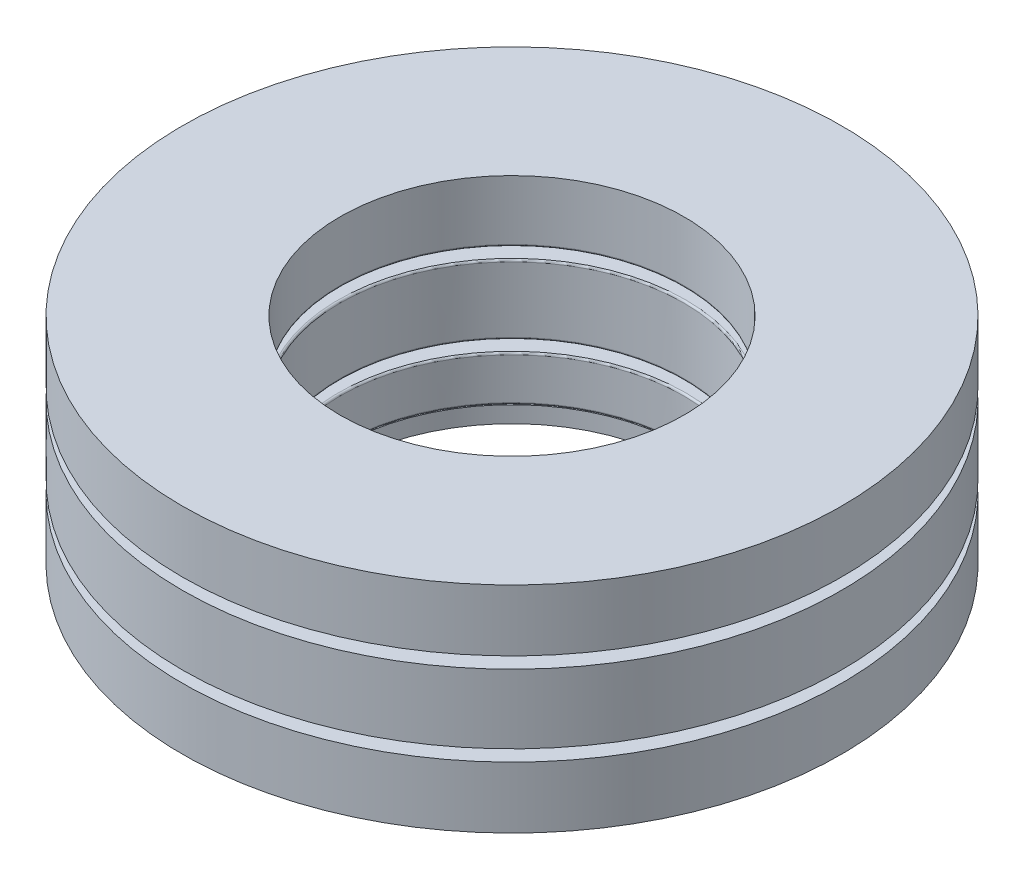
SolidWorks part; units mm, degrees
other "Imported8"
other "Imported2"
other "Imported1"
other "Imported3"
other "Imported4"
other "Imported5"
other "Imported6"
other "Imported9"
other "Imported7" parameters "Angle"=45, "Balls"=8, "D1"=8, "D2"=45, "OD"=28, "Shaft Dia"=8.0137, "Th"=8.74, "D3"=4.9022, "ID"=16.076, "E | Thickness"=4.92, "Thickness"=6.35, "Washer Thickness"=1.57, "F | Ball Diameter"=2, "Ball Diameter"=2
ref_plane "Front Plane" through (0, 0, 0) normal (0, 0, 1) x (1, 0, 0)
ref_plane "Top Plane" through (0, 0, 0) normal (0, 1, 0) x (1, 0, 0)
ref_plane "Right Plane" through (0, 0, 0) normal (1, 0, 0) x (0, 0, -1)
sketch "Sketch1" plane through (0, 0, 0) normal (0, 1, 0) x (1, 0, 0)
  circle A0 centre (0, 0) radius 12 construction
  circle A1 centre (0, 0) radius 6 construction
  circle A2 centre (0, 0) radius 9.15 construction
  dimension "OD" = 24
  dimension "Ball Circle" = 18.3
  dimension "ID" = 12
sketch "Sketch2" plane through (0, 0, 0) normal (0, 0, -1) x (-1, 0, 0)
  line L0 (-12, 3.175) -> (-12, 1.605) construction
  line L1 (-12, 0) -> (0, 0) construction
  line L3 (0, 3.175) -> (0, -3.175) construction
  line L4 (-12, 1.605) -> (-12, -1.605) construction
  line L6 (-12, -1.605) -> (-12, -3.175) construction
  point P11 (-12, 0)
sketch "Sketch3" plane through (0, 0, 0) normal (0, 0, 1) x (1, 0, 0)
  line L2 (12, 1.2038) -> (6, 1.2037)
  line L4 (12, 1.2038) -> (12, -1.2037)
  line L7 (12, -1.2037) -> (6, -1.2037)
  line L8 (6, 1.2037) -> (6, -1.2037)
  line L11 (12, 1.605) -> (12, -1.605) construction
  point P8 (6, 0)
  dimension "D1" = 2.4075
revolve "Revolve1" add sketch "Sketch3" angle 360 about L3
sketch "Sketch4" plane through (0, 0, 0) normal (0, 0, 1) x (1, 0, 0)
  line L0 (9.15, 1.605) -> (9.15, -1.605)
  arc A0 (9.15, 1.605) -> (9.15, -1.605) centre (9.15, 0) ccw
revolve "Cut-Revolve1" cut sketch "Sketch4" angle 360 about L0
sketch "Sketch5" plane through (0, 0, 0) normal (0, 0, 1) x (1, 0, 0)
  line L0 (9.15, 1.605) -> (9.15, -1.605)
  arc A0 (9.15, 1.605) -> (9.15, -1.605) centre (9.15, 0) ccw
revolve "Revolve2" add sketch "Sketch5" angle 360 about L0
pattern_circular "CirPattern1" count 8 every 45 about axis through (0, 3.175, 0) along (0, -1, 0) of bodies 187
pattern_circular "CirPattern2" count 8 every 45 about axis through (0, 0, 0) along (0, 1, 0) of "Cut-Revolve1"
sketch "Sketch6" plane through (0, 0, 0) normal (0, 0, 1) x (1, 0, 0)
  line L2 (12, 3.175) -> (6, 3.175)
  line L3 (12, 3.175) -> (12, 1.605)
  line L4 (12, 1.605) -> (6, 1.605)
  line L5 (6, 3.175) -> (6, 1.605)
  line L6 (12, -1.605) -> (6, -1.605)
  line L7 (12, -1.605) -> (12, -3.175)
  line L8 (12, -3.175) -> (6, -3.175)
  line L13 (6, -1.605) -> (6, -3.175)
  point P11 (6, 0)
revolve "Revolve3" add sketch "Sketch6" angle 360 about L3
fillet "Fillet1" radius 0.0635 4 edges at (0, 1.605, 6) (0, 1.605, 12) (0, 3.175, 12) (0, 3.175, 6)
fillet "Fillet2" radius 0.0635 20 edges at (0, -1.2037, 6) (0, -1.2037, 12) (9.15, -1.2037, 1.0616) (5.7194, -1.2037, 7.2207) (-1.0616, -1.2037, 9.15) (-7.2207, -1.2037, 5.7194) (-9.15, -1.2037, -1.0616) (-5.7194, -1.2037, -7.2207) (1.0616, -1.2037, -9.15) (0, 1.2038, 12) (0, 1.2037, 6) (9.15, 1.2037, -1.0616) (7.2207, 1.2037, 5.7194) (1.0616, 1.2037, 9.15) (-5.7194, 1.2037, 7.2207) (-9.15, 1.2037, 1.0616) (-7.2207, 1.2037, -5.7194) (-1.0616, 1.2037, -9.15) (7.2207, -1.2037, -5.7194) (5.7194, 1.2037, -7.2207)
fillet "Fillet3" radius 0.0635 4 edges at (0, -1.605, 12) (0, -1.605, 6) (0, -3.175, 6) (0, -3.175, 12)
sketch "Sketch7" plane through (0, 3.175, 0) normal (0, 1, 0) x (1, 0, 0)
  circle A0 centre (0, 0) radius 11.5
  circle A1 centre (0, 0) radius 12.5
  dimension "D1" = 23
  dimension "D2" = 25
extrude "Cut-Extrude1" cut sketch "Sketch7" against normal through all both and the other way through all
sketch "Sketch8" plane through (0, 3.175, 0) normal (0, 1, 0) x (1, 0, 0)
  circle A1 centre (0, 0) radius 11.5
  circle A2 centre (0, 0) radius 11.5
  circle A4 centre (0, 0) radius 6
  dimension "D2" = 12
  dimension "D1" = 0
extrude "Boss-Extrude1" add sketch "Sketch8" along normal blind 0.575 and the other way blind 0.3
sketch "Sketch9" plane through (0, -3.175, 0) normal (0, -1, 0) x (1, 0, 0)
  circle A0 centre (0, 0) radius 6
  circle A2 centre (0, 0) radius 11.5
  circle A3 centre (0, 0) radius 11.5
  dimension "D2" = 12
  dimension "D1" = 0
extrude "Boss-Extrude2" add sketch "Sketch9" along normal blind 0.575
equation "\"Angle@CirPattern1\" = 360/\"Balls@CirPattern1\""
equation "\"D1@CirPattern2\" = \"Balls@CirPattern1\""
equation "\"D2@CirPattern2\" = \"Angle@CirPattern1\""
equation "\"D1@Sketch3\" =  ( \"Thickness@Sketch2\" -  ( 2 * \"Washer Thickness@Sketch2\" )  )  * .75"
equation "\"D1@Fillet1\" = \"Thickness@Sketch2\" * .01"
equation "\"D1@Fillet2\"=\"D1@Fillet1\""
equation "\"D1@Fillet3\"=\"D1@Fillet1\""
